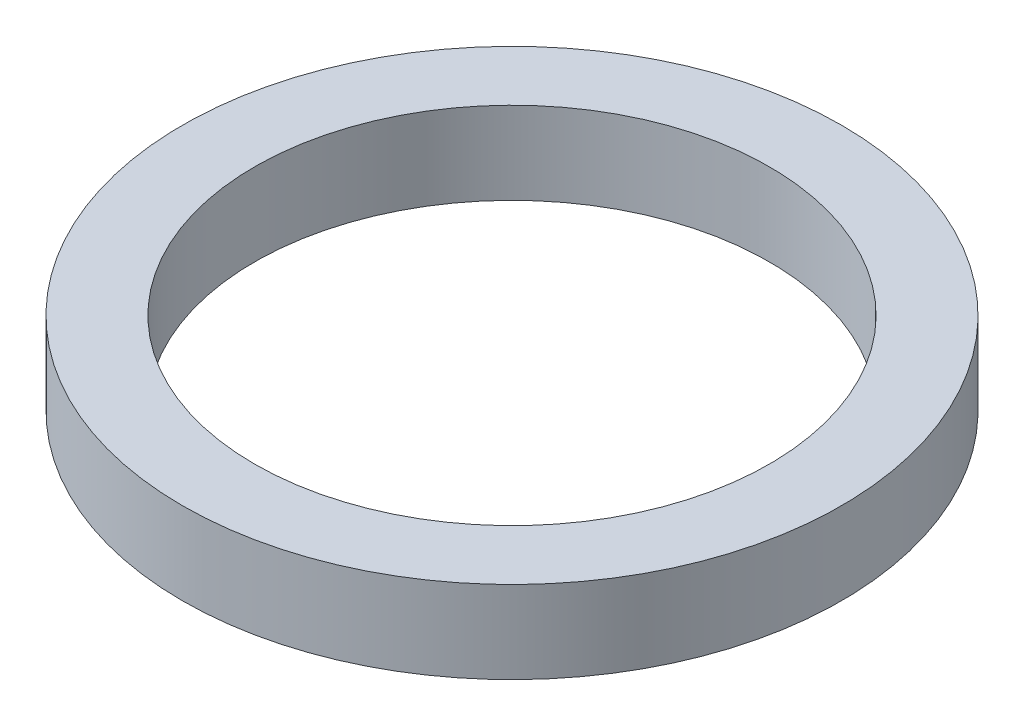
SolidWorks part; units mm, degrees
ref_plane "Front Plane" through (0, 0, 0) normal (0, 0, 1) x (1, 0, 0)
ref_plane "Top Plane" through (0, 0, 0) normal (0, 1, 0) x (1, 0, 0)
ref_plane "Right Plane" through (0, 0, 0) normal (1, 0, 0) x (0, 0, -1)
ref_plane "Plane1" through (0, 135.155, 0) normal (0, 1, 0) x (1, 0, 0)
sketch "Sketch1" plane through (0, 135.155, 0) normal (0, 1, 0) x (1, 0, 0)
  line L0 (0, 0) -> (0.5, 0)
  circle A0 centre (0.5, 0) radius 16
  circle A1 centre (0.5, 0) radius 12.5
  point P8 (-45.2245, 3.2176)
  dimension "D1" = 25
  dimension "D2" = 32
extrude "Boss-Extrude1" add sketch "Sketch1" along normal blind 4 contours A0 | A1
